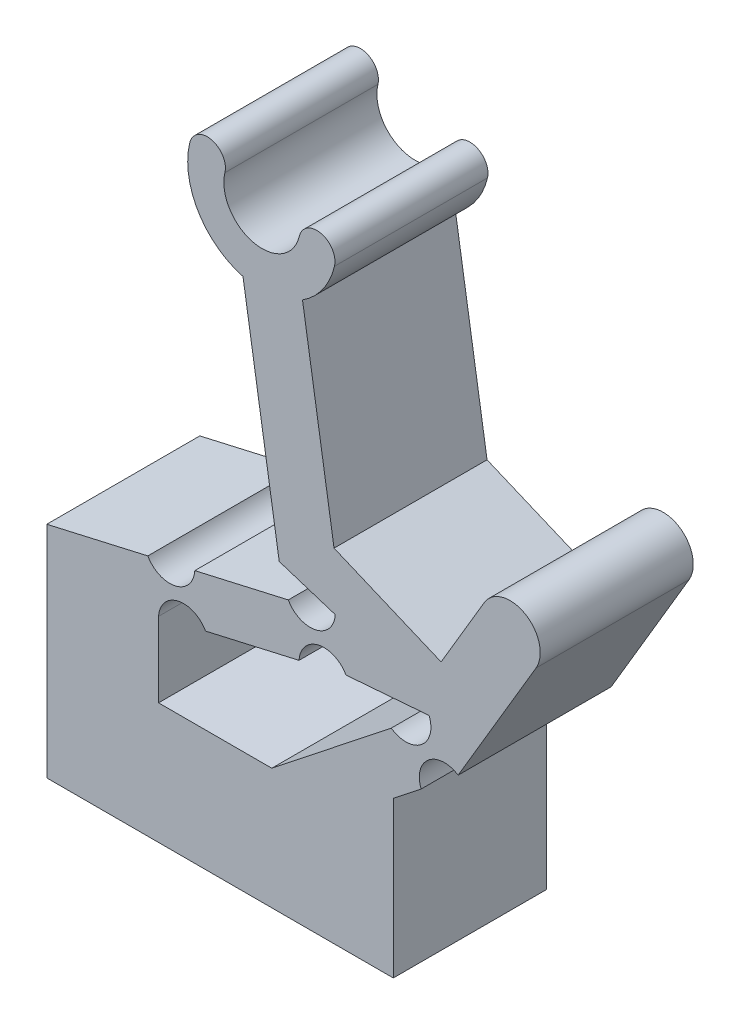
SolidWorks part; units mm, degrees
ref_plane "Front Plane" through (0, 0, 0) normal (0, 0, 1) x (1, 0, 0)
ref_plane "Top Plane" through (0, 0, 0) normal (0, 1, 0) x (1, 0, 0)
ref_plane "Right Plane" through (0, 0, 0) normal (1, 0, 0) x (0, 0, -1)
sketch "Sketch-SkeletonConfigUp" plane through (0, 0, 0) normal (0, 0, 1) x (1, 0, 0)
  line L0 (0, 0) -> (0, -50000) construction
  line L1 (0, 0) -> (5.39, -4.2111) construction
  line L2 (19.1802, -14.9852) -> (15.6997, -4.7614) construction
  line L3 (15.6997, -4.7614) -> (11.2195, -2.878) construction
  line L4 (11.2195, -2.878) -> (5.39, -4.2111) construction
  line L5 (15.6997, -4.7614) -> (19.2275, 1.2035) construction
  line L6 (11.2195, -2.878) -> (8.9358, 11.5423) construction
  line L7 (5.39, -4.2111) -> (19.1802, -14.9852) construction
  line L8 (-780.1858, 609.548) -> (19.1802, -14.9852) construction
  dimension "D2" = 6.84
  dimension "D3" = 17.5
  dimension "D4" = 10.8
  dimension "D5" = 146.8
  dimension "D6" = 4.86
  dimension "D7" = 6.93
  dimension "D8" = 14.6
  dimension "D9" = 5.98
  dimension "D10" = 82.2
  dimension "D11" = 58.2
  dimension "D12" = 52
sketch "Sketch-SkeletonConfigDown" plane through (0, 0, 0) normal (0, 0, 1) x (1, 0, 0)
  line L0 (0, 0) -> (0, -50000) construction
  line L1 (0, 0) -> (5.39, -4.2111) construction
  line L2 (19.1802, -14.9852) -> (15.6997, -4.7614) construction
  line L3 (15.6997, -4.7614) -> (11.0445, -6.1572) construction
  line L4 (11.0445, -6.1572) -> (5.39, -4.2111) construction
  line L5 (15.6997, -4.7614) -> (14.6287, 2.0853) construction
  line L6 (11.0445, -6.1572) -> (0.1113, 3.5188) construction
  line L7 (5.39, -4.2111) -> (19.1802, -14.9852) construction
  line L8 (-783.6081, 612.2217) -> (19.1802, -14.9852) construction
  dimension "D2" = 6.84
  dimension "D3" = 17.5
  dimension "D4" = 10.8
  dimension "D5" = 146.8
  dimension "D6" = 4.86
  dimension "D7" = 6.93
  dimension "D8" = 14.6
  dimension "D9" = 5.98
  dimension "D10" = 82.2
  dimension "D11" = 58.2
  dimension "D1" = 52
sketch "Sketch-ConfigUp" plane through (0, 0, 0) normal (0, 0, 1) x (1, 0, 0)
  line L1 (10.0217, -2.1261) -> (6.1419, -3.0134)
  line L4 (11.2195, -2.878) -> (5.39, -4.2111) construction
  line L5 (18.1516, 1.8398) -> (16.3632, -1.184)
  line L6 (5.39, -4.2111) -> (19.1802, -14.9852) construction
  line L9 (15.6997, -4.7614) -> (11.2195, -2.878) construction
  line L10 (11.9714, -1.6802) -> (9.6459, -0.933)
  line L11 (8.0818, -2.5697) -> (8.5277, -4.5194) construction
  line L16 (15.5355, -6.166) -> (17.1044, -4.9256) construction
  line L17 (20.3034, 0.5672) -> (17.0691, -4.9016)
  line L18 (15.6997, -4.7614) -> (19.2275, 1.2035) construction
  line L19 (17.1693, 0.1789) -> (19.3211, -1.0937) construction
  line L20 (8.1428, 8.5584) -> (9.6459, -0.933)
  line L21 (11.9211, 0.6834) -> (10.612, 8.9494)
  line L22 (11.2195, -2.878) -> (8.9358, 11.5423) construction
  line L23 (7.8403, 10.4684) -> (10.3096, 10.8594) construction
  line L26 (14.9153, -5.3816) -> (10.9257, -8.5361) construction
  line L27 (-158382.3365, 123741.843) -> (19.1802, -14.9852) construction
  line L30 (11.7512, -6.6085) -> (12.9917, -8.1774) construction
  line L38 (7.3679, 11.294) -> (8.9358, 11.5423) construction
  line L39 (8.9358, 11.5423) -> (11.938, 10.8215) construction
  line L42 (7.2022, -8.5173) -> (7.2022, -13.5356) construction
  line L43 (15.8639, -3.3567) -> (17.1044, -4.9256) construction
  line L44 (6.3648, -3.9882) -> (4.4152, -4.4341) construction
  line L46 (6.5878, -4.963) -> (4.6381, -5.4089) construction
  line L47 (14.2951, -4.5972) -> (15.5355, -6.166) construction
  line L48 (14.3798, -7.0798) -> (15.5355, -6.166)
  line L51 (11.1638, -2.6343) -> (11.2752, -3.1217) construction
  line L52 (10.0217, -2.1261) -> (10.4676, -4.0757) construction
  line L53 (11.9714, -1.6802) -> (12.4173, -3.6299) construction
  line L54 (9.3372, -8.5173) -> (9.3372, -13.5356) construction
  line L56 (10.2447, -3.1009) -> (12.1943, -2.655) construction
  line L59 (11.9714, -1.6802) -> (10.0217, -2.1261) construction
  line L61 (10.4676, -4.0757) -> (6.5878, -4.963)
  line L62 (6.1419, -3.0134) -> (6.5878, -4.963) construction
  line L67 (8.9358, 11.5423) -> (5.9337, 12.2632) construction
  line L69 (15.8548, -4.9575) -> (15.5447, -4.5653) construction
  line L71 (17.1044, -4.9256) -> (19.9366, -2.6862) construction
  line L73 (6.1419, -3.0134) -> (4.1922, -3.4592) construction
  line L77 (10.9257, -8.5361) -> (19.1802, -14.9852) construction
  line L78 (15.8639, -3.3567) -> (12.4173, -3.6299)
  line L79 (11.9211, 0.6834) -> (16.3632, -1.184)
  line L81 (14.9153, -5.3816) -> (16.4841, -4.1412) construction
  line L82 (17.1693, 0.1789) -> (16.3632, -1.184) construction
  line L92 (7.2022, -8.5173) -> (9.3372, -8.5173)
  line L93 (5.3343, -3.9674) -> (5.4457, -4.4548) construction
  line L94 (14.3798, -13.5356) -> (14.3798, -7.0798)
  line L108 (0, -4.418) -> (0, -13.5356)
  line L109 (0, -13.5356) -> (14.3798, -13.5356)
  line L115 (4.1922, -3.4592) -> (0, -4.418)
  line L116 (14.2814, -4.608) -> (14.2951, -4.5972)
  line L117 (14.2951, -4.5972) -> (15.8639, -3.3567) construction
  line L121 (12.4173, -3.6299) -> (10.4676, -4.0757) construction
  line L125 (4.6381, -5.4089) -> (4.6381, -8.5173)
  line L126 (14.2814, -4.608) -> (9.3372, -8.5173)
  line L128 (11.9211, 0.6834) -> (13.025, -6.2872) construction
  line L129 (4.1922, -3.4592) -> (4.6381, -5.4089) construction
  line L130 (4.6381, -8.5173) -> (7.2022, -8.5173)
  line L131 (9.3372, -8.5173) -> (14.3798, -8.5173) construction
  line L132 (0, 200000) -> (0, -250000) construction
  arc A0 (18.1516, 1.8398) -> (20.3034, 0.5672) centre (19.2275, 1.2035) cw
  arc A2 (7.3922, 11.913) -> (10.4795, 11.1717) centre (8.9358, 11.5423) ccw
  arc A3 (10.612, 8.9494) -> (11.938, 10.8215) centre (8.9358, 11.5423) ccw
  arc A4 (5.9337, 12.2632) -> (7.3922, 11.913) centre (6.6629, 12.0881) cw
  arc A5 (11.938, 10.8215) -> (10.4795, 11.1717) centre (11.2088, 10.9966) ccw
  arc A6 (5.9337, 12.2632) -> (8.1428, 8.5584) centre (8.9358, 11.5423) ccw
  arc A7 (10.4676, -4.0757) -> (12.4173, -3.6299) centre (11.5075, -4.1371) cw
  arc A15 (6.5878, -4.963) -> (4.6381, -5.4089) centre (5.678, -5.4703) ccw
  arc A21 (10.0217, -2.1261) -> (11.9714, -1.6802) centre (10.9315, -1.6188) ccw
  arc A42 (6.1419, -3.0134) -> (4.1922, -3.4592) centre (5.102, -2.952) cw
  arc A43 (15.5355, -6.166) -> (17.0691, -4.9016) centre (16.5008, -5.7746) cw
  arc A44 (14.2951, -4.5972) -> (15.8639, -3.3567) centre (14.8986, -3.7482) ccw
  point P1 (10.0217, -2.1261)
  point P4 (0, 0)
  point P19 (11.938, -1.6188)
  point P20 (11.938, -1.6188)
  point P23 (9.6529, -0.933)
  point P27 (8.3047, -3.5445)
  point P28 (-13.3686, -7.4752)
  point P32 (18.47, -3.8597)
  point P34 (19.9559, -2.655)
  point P38 (18.2452, -0.4574)
  point P45 (14.2957, -4.5916)
  point P51 (9.075, 10.6639)
  point P61 (12.3715, -7.393)
  point P71 (17.0677, -4.9039)
  point P72 (0, -4.4341)
  point P78 (0, 0)
  point P125 (5.4457, -4.4548)
  point P130 (5.3343, -3.9674)
  dimension "D3" = 3.175
  dimension "D4" = 6.175
  dimension "D6" = 2
  dimension "D10" = 2
  dimension "D14" = 22.5
  dimension "D16" = 2.5
  dimension "D21" = 22.5
  dimension "D11" = 0.5
  dimension "D7" = 0.5
  dimension "D9" = 2
  dimension "D22" = 2
  dimension "D24" = 0.5
extrude "Boss-Extrude1" add sketch "Sketch-ConfigUp" along normal blind 6.35
equation "\"axle-diameter\"=2"
equation "\"switch-thickness\"=12"
equation "\"base-width\"=4.0"
equation "\"axle-bushing-radius\"=3"
equation "\"clearance\"= 0.25"
equation "\"arm-width\"=1.5"
equation "\"min-diameter\"=70"
equation "\"alpha\"=52.0"
equation "\"beta\"=19.3"
equation "\"gamma\"=146.8"
equation "\"delta\"=58.2"
equation "\"epsilon\"=82.2"
equation "\"eta\"=-272.1"
equation "\"l_AB\"=17.5"
equation "\"l_AC\"=5.98"
equation "\"l_BD\"=10.8"
equation "\"l_CD\"=4.86"
equation "\"l_CE\"=14.6"
equation "\"l_DF\"=6.93"
equation "\"l_OA\"=6.84"
equation "\"D2@Sketch-SkeletonConfigUp\" = \"l_OA\""
equation "\"D3@Sketch-SkeletonConfigUp\" = \"l_AB\""
equation "\"D4@Sketch-SkeletonConfigUp\" = \"l_BD\""
equation "\"D5@Sketch-SkeletonConfigUp\" = \"gamma\""
equation "\"D6@Sketch-SkeletonConfigUp\" = \"l_CD\""
equation "\"D7@Sketch-SkeletonConfigUp\" = \"l_DF\""
equation "\"D8@Sketch-SkeletonConfigUp\" = \"l_CE\""
equation "\"D9@Sketch-SkeletonConfigUp\" = \"l_AC\""
equation "\"D_groove\"=3.175"
equation "\"D7@Sketch-SkeletonConfigDown\" = \"l_DF\""
equation "\"D6@Sketch-SkeletonConfigDown\" = \"l_CD\""
equation "\"D2@Sketch-SkeletonConfigDown\" = \"l_OA\""
equation "\"D3@Sketch-SkeletonConfigDown\" = \"l_AB\""
equation "\"D9@Sketch-SkeletonConfigDown\" = \"l_AC\""
equation "\"D8@Sketch-SkeletonConfigDown\" = \"l_CE\""
equation "\"D5@Sketch-SkeletonConfigDown\" = \"gamma\""
equation "\"D4@Sketch-SkeletonConfigDown\" = \"l_BD\""
equation "\"D1@Sketch-SkeletonConfigDown\" = \"alpha\""
equation "\"hinge_length\"=1.5"
equation "\"hinge_depth\"=0.25"
equation "\"D10@Sketch-SkeletonConfigUp\"=\"epsilon\""
equation "\"D11@Sketch-SkeletonConfigUp\"=\"delta\""
equation "\"D12@Sketch-SkeletonConfigUp\"=\"alpha\""
equation "\"D11@Sketch-SkeletonConfigDown\"=\"delta\""
equation "\"D10@Sketch-SkeletonConfigDown\"=\"epsilon\""
equation "\"EE_dx\"=8.74"
equation "\"EE_dy\"=8.0"
equation "\"r_groove\"=\"D_groove\"/2"
equation "\"t_wall\"=25.4/16"
equation "\"width_lower\"=\"D_groove\"+\"t_wall\""
equation "\"cable_to_bottom\"=30.6257"
